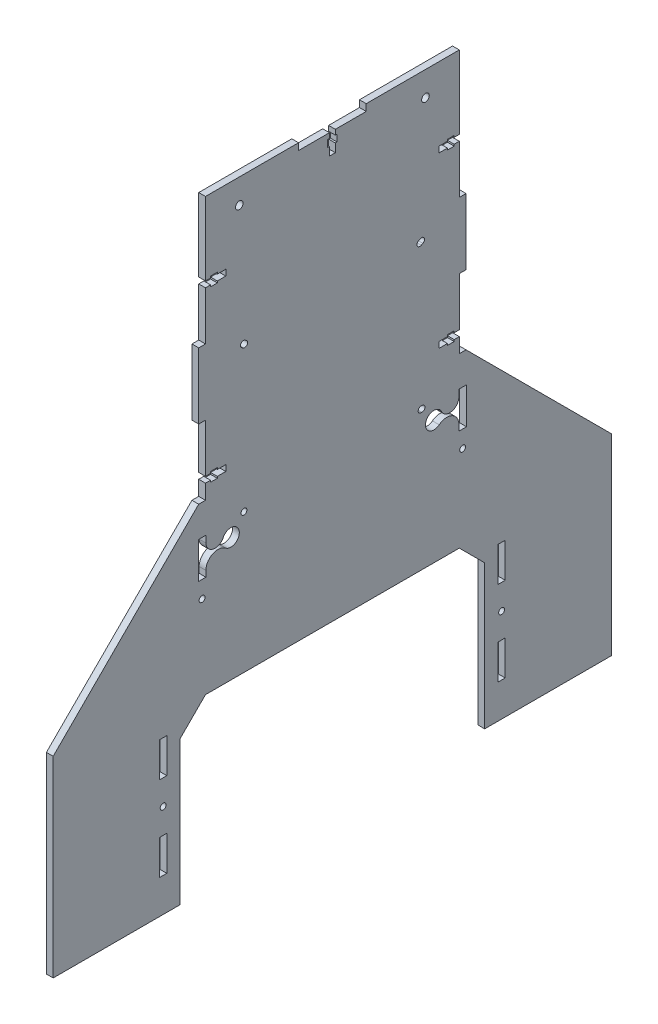
SolidWorks part; units mm, degrees
material "1060 Alloy"
ref_plane "Front Plane" through (0, 0, 0) normal (0, 0, 1) x (1, 0, 0)
ref_plane "Top Plane" through (0, 0, 0) normal (0, 1, 0) x (1, 0, 0)
ref_plane "Right Plane" through (0, 0, 0) normal (1, 0, 0) x (0, 0, -1)
sketch "Sketch1" plane through (0, 0, 0) normal (1, 0, 0) x (0, 0, -1)
  line L1 (-75, 0) -> (75, 0)
  line L2 (-75, 0) -> (-75, -255)
  line L3 (-75, -255) -> (75, -255)
  line L4 (75, 0) -> (75, -255)
  dimension "D1" = 150
  dimension "D2" = 255
sheet metal parameters "Sheet-Metal1" thickness 4 parameters "D1"=5
base flange "Base-Flange1" sketch "Sketch1" thickness 4 reverse thickness direction no parameters "D1"=5
sketch "Sketch4" plane through (0, 0, 0) normal (1, 0, 0) x (0, 0, -1)
  line L0 (-75, -43.25) -> (-75, -46.75)
  line L1 (-75, 0) -> (-75, -255) construction
  line L2 (-75, 0) -> (-75, -255) construction
  line L3 (-75, -46.75) -> (-72, -46.75)
  line L4 (-72, -46.75) -> (-72, -47.75)
  line L5 (-72, -47.75) -> (-68, -47.75)
  line L6 (-68, -47.75) -> (-68, -46.75)
  line L7 (-68, -46.75) -> (-63, -46.75)
  line L8 (-63, -46.75) -> (-63, -43.25)
  line L9 (-63, -43.25) -> (-68, -43.25)
  line L10 (-68, -43.25) -> (-68, -42.25)
  line L11 (-68, -42.25) -> (-72, -42.25)
  line L12 (-72, -42.25) -> (-72, -43.25)
  line L13 (-72, -43.25) -> (-75, -43.25)
  line L14 (-75, -95) -> (75, -95) construction
  line L15 (75, -255) -> (75, 0) construction
  line L16 (0, -95) -> (0, 0) construction
  line L17 (-75, -45) -> (-63, -45) construction
  line L18 (75, 0) -> (-75, 0) construction
  line L19 (-75, -145) -> (-63, -145) construction
  line L20 (-72, -146.75) -> (-75, -146.75)
  line L21 (-72, -147.75) -> (-72, -146.75)
  line L22 (-68, -147.75) -> (-72, -147.75)
  line L23 (-68, -146.75) -> (-68, -147.75)
  line L24 (-63, -146.75) -> (-68, -146.75)
  line L25 (-63, -143.25) -> (-63, -146.75)
  line L26 (-68, -143.25) -> (-63, -143.25)
  line L27 (-68, -142.25) -> (-68, -143.25)
  line L28 (-72, -142.25) -> (-68, -142.25)
  line L29 (-72, -143.25) -> (-72, -142.25)
  line L30 (-75, -143.25) -> (-72, -143.25)
  line L31 (-75, -146.75) -> (-75, -143.25)
  line L32 (75, -145) -> (63, -145) construction
  line L33 (75, -146.75) -> (75, -143.25)
  line L34 (75, -143.25) -> (72, -143.25)
  line L35 (72, -143.25) -> (72, -142.25)
  line L36 (72, -142.25) -> (68, -142.25)
  line L37 (68, -142.25) -> (68, -143.25)
  line L38 (68, -143.25) -> (63, -143.25)
  line L39 (63, -143.25) -> (63, -146.75)
  line L40 (63, -146.75) -> (68, -146.75)
  line L41 (68, -146.75) -> (68, -147.75)
  line L42 (68, -147.75) -> (72, -147.75)
  line L43 (72, -147.75) -> (72, -146.75)
  line L44 (72, -146.75) -> (75, -146.75)
  line L45 (75, -45) -> (63, -45) construction
  line L46 (72, -43.25) -> (75, -43.25)
  line L47 (72, -42.25) -> (72, -43.25)
  line L48 (68, -42.25) -> (72, -42.25)
  line L49 (68, -43.25) -> (68, -42.25)
  line L50 (63, -43.25) -> (68, -43.25)
  line L51 (63, -46.75) -> (63, -43.25)
  line L52 (68, -46.75) -> (63, -46.75)
  line L53 (68, -47.75) -> (68, -46.75)
  line L54 (72, -47.75) -> (68, -47.75)
  line L55 (72, -46.75) -> (72, -47.75)
  line L56 (75, -46.75) -> (72, -46.75)
  line L57 (75, -43.25) -> (75, -46.75)
  dimension "D1" = 3.5
  dimension "D2" = 5.5
  dimension "D3" = 4
  dimension "D4" = 3
  dimension "D5" = 5
  dimension "D6" = 45
  dimension "D7" = 100
extrude "Cut-Extrude1" cut sketch "Sketch4" against normal through all normal cut yes
sketch "Sketch5" plane through (0, 0, 0) normal (1, 0, 0) x (0, 0, -1)
  line L0 (-75, -43.25) -> (-75, -46.75) construction
  line L1 (-75, -143.25) -> (-75, -146.75) construction
  line L2 (-75, -145) -> (-75, -45) construction
  line L3 (-75, -95) -> (-79, -95) construction
  line L4 (0, 0) -> (0, -255) construction
  line L5 (-79, -75.5) -> (-75, -75.5)
  line L6 (-79, -75.5) -> (-79, -114.5)
  line L7 (-79, -114.5) -> (-75, -114.5)
  line L8 (-75, -75.5) -> (-75, -114.5)
  line L9 (-75, -255) -> (75, -255) construction
  line L10 (75, -95) -> (79, -95) construction
  line L11 (75, -145) -> (75, -45) construction
  line L12 (75, -143.25) -> (75, -146.75) construction
  line L13 (75, -43.25) -> (75, -46.75) construction
  line L14 (75, -75.5) -> (75, -114.5)
  line L15 (79, -114.5) -> (75, -114.5)
  line L16 (79, -75.5) -> (79, -114.5)
  line L17 (79, -75.5) -> (75, -75.5)
  line L19 (-19, -255) -> (19, -255) construction
  line L20 (-19, -255) -> (-19, -259) construction
  line L21 (-19, -259) -> (19, -259) construction
  line L22 (19, -255) -> (19, -259) construction
  dimension "D1" = 4
  dimension "D2" = 39
  dimension "D3" = 38
  dimension "D4" = 4
base flange "Tab1" sketch "Sketch5" thickness 4 reverse thickness direction no parameters "D1"=5
sketch "Sketch6" plane through (0, 0, 0) normal (1, 0, 0) x (0, 0, -1)
  line L0 (-55, -14.5) -> (-67, -14.5) construction
  line L1 (75, 0) -> (-75, 0) construction
  line L2 (-75, 0) -> (-75, -43.25) construction
  line L3 (0, 0) -> (0, -14.1552) construction
  line L4 (55, -14.5) -> (67, -14.5) construction
  circle A0 centre (-67, -14.5) radius 2.25 construction
  circle A1 centre (-55, -14.5) radius 2.25
  circle A2 centre (55, -14.5) radius 2.25
  circle A3 centre (67, -14.5) radius 2.25 construction
  dimension "D1" = 4.5
  dimension "D4" = 8
  dimension "D2" = 12
  dimension "D3" = 14.5
extrude "Cut-Extrude2" cut sketch "Sketch6" against normal through all normal cut yes
sketch "Sketch7" plane through (0, 0, 0) normal (1, 0, 0) x (0, 0, -1)
  line L0 (-75, -255) -> (-90, -270)
  line L1 (-90, -270) -> (-90, -355)
  line L2 (-90, -355) -> (-165, -355)
  line L3 (-165, -355) -> (-165, -241.5)
  line L4 (-75, -155.5) -> (-79, -155.5)
  line L5 (-75, -146.75) -> (-75, -255) construction
  line L6 (-75, -155.5) -> (-75, -255)
  line L7 (0, -255) -> (0, 0) construction
  line L8 (-75, -255) -> (75, -255) construction
  line L9 (75, -155.5) -> (75, -255)
  line L10 (-79, -155.5) -> (-165, -241.5)
  line L11 (165, -355) -> (165, -241.5)
  line L12 (90, -355) -> (165, -355)
  line L13 (90, -270) -> (90, -355)
  line L14 (75, -255) -> (90, -270)
  line L15 (79, -155.5) -> (165, -241.5)
  line L16 (75, -155.5) -> (79, -155.5)
  dimension "D1" = 4
  dimension "D2" = 15
  dimension "D3" = 75
  dimension "D4" = 100
  dimension "D5" = 45
  dimension "D6" = 99.5
base flange "Tab2" sketch "Sketch7" thickness 4 reverse thickness direction no parameters "D1"=5
sketch "Sketch8" plane through (0, 0, 0) normal (1, 0, 0) x (0, 0, -1)
  line L0 (77, -155.5) -> (77, -205) construction
  line L2 (79, -155.5) -> (75, -155.5) construction
  line L3 (77, -205) -> (-77, -205) construction
  line L4 (-77, -205) -> (-77, -155.5) construction
  line L5 (-75, -155.5) -> (-79, -155.5) construction
  line L6 (-75, -255) -> (75, -255) construction
  circle A0 centre (-77, -205) radius 1.75
  circle A1 centre (77, -205) radius 1.75
  dimension "D2" = 3.5
  dimension "D1" = 50
extrude "Cut-Extrude3" cut sketch "Sketch8" against normal through all normal cut yes
sketch "Sketch9" plane through (0, 0, 0) normal (1, 0, 0) x (0, 0, -1)
  line L0 (-165, -355) -> (-90, -355) construction
  line L1 (-138, -355) -> (-117, -355)
  line L2 (-138, -355) -> (-138, -351)
  line L3 (-138, -351) -> (-129.25, -351)
  line L4 (-117, -355) -> (-117, -351)
  line L6 (-125.75, -351) -> (-117, -351)
  line L7 (0, -255) -> (0, -355) construction
  line L8 (-75, -255) -> (75, -255) construction
  line L9 (138, -355) -> (165, -355) construction
  line L10 (117, -355) -> (90, -355) construction
  line L11 (125.75, -348) -> (125.75, -351)
  line L12 (-117, -355) -> (-90, -355) construction
  line L13 (-138, -355) -> (-165, -355) construction
  line L14 (-129.25, -351) -> (-129.25, -348)
  line L15 (-129.25, -348) -> (-130.25, -348)
  line L16 (-130.25, -348) -> (-130.25, -344)
  line L17 (-130.25, -344) -> (-129.25, -344)
  line L18 (-129.25, -344) -> (-129.25, -339)
  line L19 (-129.25, -339) -> (-125.75, -339)
  line L20 (-125.75, -339) -> (-125.75, -344)
  line L21 (-125.75, -344) -> (-124.75, -344)
  line L22 (-124.75, -344) -> (-124.75, -348)
  line L23 (-124.75, -348) -> (-125.75, -348)
  line L24 (-125.75, -348) -> (-125.75, -351)
  line L25 (124.75, -348) -> (125.75, -348)
  line L26 (124.75, -344) -> (124.75, -348)
  line L27 (125.75, -344) -> (124.75, -344)
  line L28 (125.75, -339) -> (125.75, -344)
  line L29 (129.25, -339) -> (125.75, -339)
  line L30 (129.25, -344) -> (129.25, -339)
  line L31 (130.25, -344) -> (129.25, -344)
  line L32 (130.25, -348) -> (130.25, -344)
  line L33 (129.25, -348) -> (130.25, -348)
  line L34 (129.25, -351) -> (129.25, -348)
  line L35 (125.75, -351) -> (117, -351)
  line L36 (117, -355) -> (117, -351)
  line L37 (138, -351) -> (129.25, -351)
  line L38 (138, -355) -> (138, -351)
  line L39 (138, -355) -> (117, -355)
  dimension "D1" = 21
  dimension "D2" = 4
  dimension "D3" = 3.5
  dimension "D4" = 5.5
  dimension "D5" = 3
  dimension "D6" = 4
  dimension "D7" = 5
sketch "Sketch10" plane through (0, 0, 0) normal (1, 0, 0) x (0, 0, -1)
  line L0 (-100, -285) -> (-100, -314.5) construction
  line L1 (-102.15, -314.5) -> (-97.85, -314.5)
  line L2 (-102.15, -314.5) -> (-102.15, -335)
  line L3 (-102.15, -335) -> (-97.85, -335)
  line L4 (-97.85, -314.5) -> (-97.85, -335)
  line L5 (-102.15, -285) -> (-97.85, -285)
  line L6 (-102.15, -285) -> (-102.15, -264.5)
  line L7 (-102.15, -264.5) -> (-97.85, -264.5)
  line L8 (-97.85, -285) -> (-97.85, -264.5)
  line L9 (-100, -335) -> (-100, -355) construction
  line L11 (-165, -355) -> (-90, -355) construction
  line L12 (-102.15, -324.75) -> (-97.85, -324.75) construction
  line L13 (-102.15, -274.75) -> (-97.85, -274.75) construction
  line L14 (0, -255) -> (0, -297.2128) construction
  line L15 (-75, -255) -> (75, -255) construction
  line L16 (102.15, -274.75) -> (97.85, -274.75) construction
  line L17 (102.15, -324.75) -> (97.85, -324.75) construction
  line L18 (100, -335) -> (100, -355) construction
  line L19 (100, -285) -> (100, -314.5) construction
  line L20 (97.85, -285) -> (97.85, -264.5)
  line L21 (102.15, -264.5) -> (97.85, -264.5)
  line L22 (102.15, -285) -> (102.15, -264.5)
  line L23 (102.15, -285) -> (97.85, -285)
  line L24 (97.85, -314.5) -> (97.85, -335)
  line L25 (102.15, -335) -> (97.85, -335)
  line L26 (102.15, -314.5) -> (102.15, -335)
  line L27 (102.15, -314.5) -> (97.85, -314.5)
  circle A0 centre (-100, -299.75) radius 1.75
  circle A1 centre (100, -299.75) radius 1.75
  dimension "D6" = 3.5
  dimension "D1" = 4.3
  dimension "D2" = 20
  dimension "D3" = 20.5
  dimension "D4" = 50
  dimension "D5" = 100
extrude "Cut-Extrude5" cut sketch "Sketch10" against normal through all normal cut yes
sketch "Sketch11" plane through (0, 0, 0) normal (1, 0, 0) x (0, 0, -1)
  line L0 (-20, 0) -> (-20, -4)
  line L1 (-75, 0) -> (75, 0) construction
  line L2 (-20, -4) -> (-1.75, -4)
  line L3 (-1.75, -4) -> (-1.75, -7)
  line L4 (-1.75, -7) -> (-2.75, -7)
  line L5 (-2.75, -7) -> (-2.75, -11)
  line L6 (-2.75, -11) -> (-1.75, -11)
  line L7 (-1.75, -11) -> (-1.75, -16)
  line L8 (-1.75, -16) -> (1.75, -16)
  line L9 (1.75, -16) -> (1.75, -11)
  line L10 (1.75, -11) -> (2.75, -11)
  line L11 (2.75, -11) -> (2.75, -7)
  line L12 (2.75, -7) -> (1.75, -7)
  line L13 (1.75, -7) -> (1.75, -4)
  line L14 (1.75, -4) -> (20, -4)
  line L15 (20, -4) -> (20, 0)
  line L16 (75, 0) -> (-75, 0) construction
  line L17 (20, 0) -> (-20, 0)
  dimension "D1" = 3.5
  dimension "D2" = 5.5
  dimension "D3" = 3
  dimension "D4" = 4
  dimension "D5" = 5
  dimension "D6" = 4
  dimension "D7" = 40
extrude "Cut-Extrude6" cut sketch "Sketch11" against normal through all normal cut yes
sketch "Sketch12" plane through (0, 0, 0) normal (1, 0, 0) x (0, 0, -1)
  line L0 (-77, -155.5) -> (-77, -173.5) construction
  line L1 (-75, -155.5) -> (-79, -155.5) construction
  line L2 (0, -255) -> (0, -120.0949) construction
  line L3 (-79.25, -173.5) -> (-74.75, -173.5)
  line L4 (-79.25, -173.5) -> (-79.25, -195)
  line L5 (-79.25, -195) -> (-74.75, -195)
  line L6 (-74.75, -173.5) -> (-74.75, -195)
  line L7 (-75, -255) -> (75, -255) construction
  line L8 (77, -155.5) -> (77, -173.5) construction
  line L9 (74.75, -173.5) -> (74.75, -195)
  line L10 (79.25, -195) -> (74.75, -195)
  line L11 (79.25, -173.5) -> (79.25, -195)
  line L12 (79.25, -173.5) -> (74.75, -173.5)
  dimension "D1" = 4.5
  dimension "D2" = 18
  dimension "D3" = 21.5
extrude "Cut-Extrude7" cut sketch "Sketch12" against normal through all normal cut yes
sketch "Sketch14" plane through (-4, 0, 0) normal (-1, 0, 0) x (0, 1, 0)
  line L0 (-84.5, 54.75) -> (-175, -54.75) construction
  line L1 (-84.5, 54.75) -> (-84.5, -54.75) construction
  line L2 (-84.5, 54.75) -> (-175, 54.75) construction
  line L3 (-175, 54.75) -> (-175, -54.75) construction
  line L4 (-84.5, -54.75) -> (-175, -54.75) construction
  line L5 (-129.75, 0) -> (-129.75, -79) construction
  line L6 (-75.5, -79) -> (-114.5, -79) construction
  line L7 (-129.75, 0) -> (-129.75, 79) construction
  line L8 (-114.5, 79) -> (-75.5, 79) construction
  line L9 (-255, -75) -> (-255, 75) construction
  circle A0 centre (-172.7, 52.45) radius 1.75
  circle A1 centre (-142.2, 29.75) radius 1.75 construction
  circle A2 centre (-172.7, -52.25) radius 1.75
  circle A3 centre (-86.7, -52.55) radius 1.75
  circle A4 centre (-87.2, 51.75) radius 1.75
  circle A5 centre (-137.2, 3.25) radius 1.75 construction
  circle A6 centre (-114, -52.75) radius 1.75 construction
  dimension "D3" = 3.5
  dimension "D4" = 2.3
  dimension "D5" = 2.3
  dimension "D6" = 107
  dimension "D7" = 2.3
  dimension "D9" = 32.8
  dimension "D11" = 37.8
  dimension "D13" = 87.8
  dimension "D15" = 88.3
  dimension "D17" = 61
  dimension "D1" = 90.5
  dimension "D2" = 109.5
  dimension "D8" = 25
  dimension "D10" = 51.5
  dimension "D12" = 3
  dimension "D14" = 107.3
  dimension "D16" = 107.5
  dimension "D18" = 80
extrude "Cut-Extrude9" cut sketch "Sketch14" against normal through all normal cut yes
sketch "Sketch16" plane through (0, 0, 0) normal (1, 0, 0) x (0, 0, -1)
  line L0 (-60, -182) -> (60, -182) construction
  line L1 (0, -182) -> (0, -255) construction
  line L2 (-75, -255) -> (75, -255) construction
  line L4 (-74.75, -177.5) -> (-74.75, -191.5)
  line L5 (74.75, -177.5) -> (74.75, -191.5)
  arc A0 (-63.121, -185.9063) -> (-64.5065, -179.834) centre (-60, -182) ccw
  arc A1 (74.75, -177.5) -> (64.5065, -179.834) centre (69.3623, -177.5) cw
  arc A2 (-74.75, -191.5) -> (-63.121, -185.9063) centre (-67.5902, -191.5) cw
  arc A3 (-74.75, -177.5) -> (-64.5065, -179.834) centre (-69.3623, -177.5) ccw
  arc A4 (74.75, -191.5) -> (63.121, -185.9063) centre (67.5902, -191.5) ccw
  arc A5 (63.121, -185.9063) -> (64.5065, -179.834) centre (60, -182) cw
  dimension "D3" = 5
  dimension "D1" = 73
  dimension "D2" = 120
  dimension "D4" = 9.5
  dimension "D5" = 4.5
  dimension "D6" = 14.75
extrude "Cut-Extrude11" cut sketch "Sketch16" against normal through all normal cut yes
sketch "Sketch17" plane through (0, 0, 0) normal (1, 0, 0) x (0, 0, -1)
  line L0 (52.45, -172.7) -> (52.95, -172.7) construction
  line L1 (52.45, -170.95) -> (52.95, -170.95)
  line L2 (52.45, -174.45) -> (52.95, -174.45)
  line L3 (-52.55, -86.7) -> (-51.85, -87.2) construction
  line L4 (-51.5328, -85.276) -> (-50.8328, -85.776)
  line L5 (-53.5672, -88.124) -> (-52.8672, -88.624)
  line L6 (51.75, -87.2) -> (52.75, -86.7) construction
  line L7 (50.9674, -85.6348) -> (51.9674, -85.1348)
  line L8 (52.5326, -88.7652) -> (53.5326, -88.2652)
  arc A0 (52.45, -170.95) -> (52.45, -174.45) centre (52.45, -172.7) ccw
  arc A1 (52.95, -174.45) -> (52.95, -170.95) centre (52.95, -172.7) ccw
  circle A2 centre (52.45, -172.7) radius 1.75 construction
  circle A3 centre (-52.25, -172.7) radius 1.75 construction
  arc A4 (-51.5328, -85.276) -> (-53.5672, -88.124) centre (-52.55, -86.7) ccw
  arc A5 (-52.8672, -88.624) -> (-50.8328, -85.776) centre (-51.85, -87.2) ccw
  circle A6 centre (-52.55, -86.7) radius 1.75 construction
  arc A8 (50.9674, -85.6348) -> (52.5326, -88.7652) centre (51.75, -87.2) ccw
  arc A9 (53.5326, -88.2652) -> (51.9674, -85.1348) centre (52.75, -86.7) ccw
  circle A10 centre (51.75, -87.2) radius 1.75 construction
  point P3 (52.7, -172.7)
  point P15 (-52.2, -86.95)
  point P25 (52.25, -86.95)
  dimension "D1" = 105.2
  dimension "D3" = 85.5
  dimension "D5" = 105
  dimension "D2" = 0.7
  dimension "D4" = 86
extrude "Cut-Extrude12" cut sketch "Sketch17" against normal through all normal cut yes
flat pattern "Flat-Pattern1" [suppressed]
sketch "Bend-Lines1" plane through (0, 0, 0) normal (0, 1, 0) x (1, 0, 0)
sketch3d "Bounding-Box1" [suppressed]
  line L0 (165, 0, 0) -> (165, -355, 0) construction
  line L1 (-165, 0, 0) -> (-165, -355, 0) construction
  line L2 (165, 0, 0) -> (-165, 0, 0) construction
  line L3 (165, -355, 0) -> (-165, -355, 0) construction
